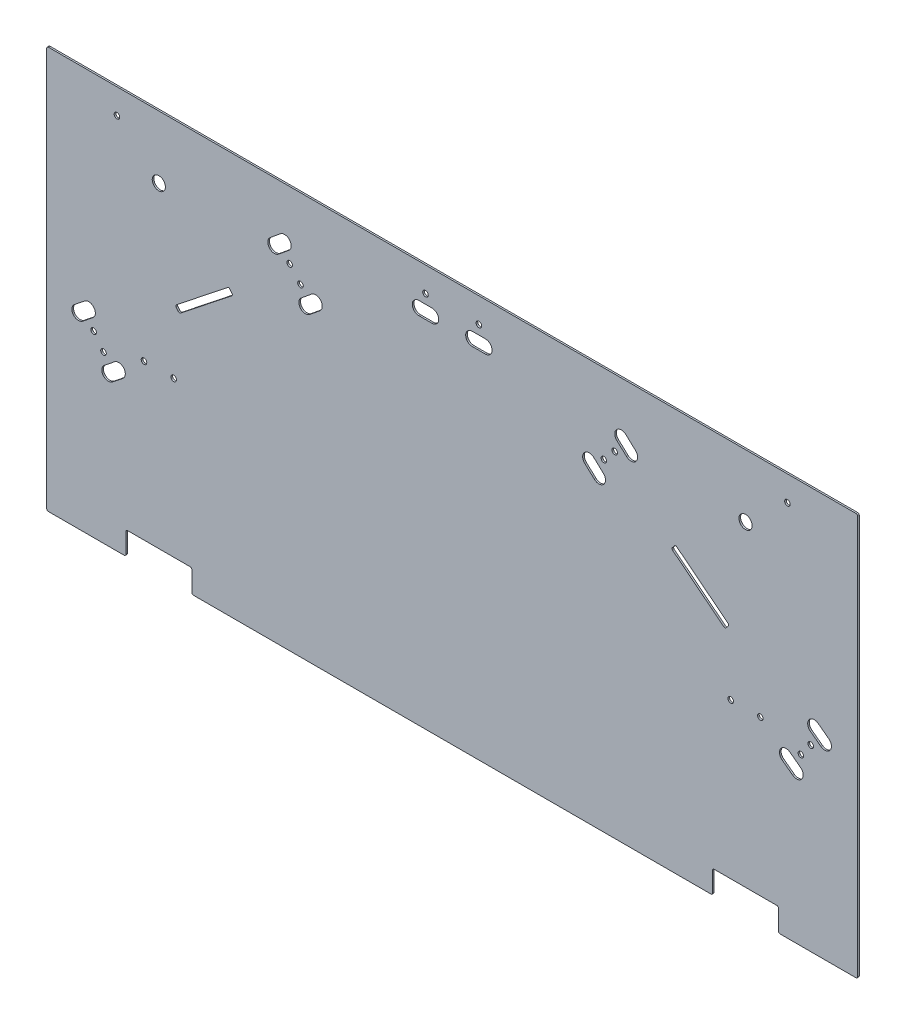
SolidWorks part; units mm, degrees
material "PE High Density"
ref_plane "Front Plane" through (0, 0, 0) normal (0, 0, 1) x (1, 0, 0)
ref_plane "Top Plane" through (0, 0, 0) normal (0, 1, 0) x (1, 0, 0)
ref_plane "Right Plane" through (0, 0, 0) normal (1, 0, 0) x (0, 0, -1)
sketch "Sketch1" plane through (0, 0, 0) normal (0, 0, 1) x (1, 0, 0)
  line L1 (-781.05, 387.35) -> (781.05, 387.35)
  line L2 (-781.05, 387.35) -> (-781.05, -387.35)
  line L3 (-781.05, -387.35) -> (781.05, -387.35)
  line L4 (781.05, 387.35) -> (781.05, -387.35)
  line L5 (-781.05, 387.35) -> (781.05, -387.35) construction
  line L6 (-781.05, -387.35) -> (781.05, 387.35) construction
  line L7 (-533.6334, 78.9622) -> (-525.7417, 69.0118)
  line L8 (-542.925, 342.9) -> (-542.925, -501.65) construction
  line L9 (542.925, 342.9) -> (542.925, -501.65) construction
  line L11 (587.375, 342.9) -> (587.375, -501.65) construction
  line L12 (-587.375, 342.9) -> (-587.375, -501.65) construction
  line L21 (-628.65, -387.35) -> (-501.65, -387.35)
  line L22 (-628.65, -387.35) -> (-628.65, -342.9)
  line L23 (-628.65, -342.9) -> (-501.65, -342.9)
  line L24 (-501.65, -387.35) -> (-501.65, -342.9)
  line L25 (628.65, -387.35) -> (501.65, -387.35)
  line L26 (628.65, -387.35) -> (628.65, -342.9)
  line L27 (628.65, -342.9) -> (501.65, -342.9)
  line L28 (501.65, -387.35) -> (501.65, -342.9)
  line L32 (-525.7417, 69.0118) -> (-422.2573, 151.0856)
  line L33 (-422.2573, 151.0856) -> (-430.149, 161.036)
  line L34 (-430.149, 161.036) -> (-533.6334, 78.9622)
  line L36 (525.8301, 69.1038) -> (422.2669, 151.078)
  line L37 (422.2669, 151.078) -> (430.149, 161.036)
  line L38 (430.149, 161.036) -> (533.7123, 79.0618)
  line L39 (533.7123, 79.0618) -> (525.8301, 69.1038)
  circle A0 centre (-51.435, 339.4592) radius 5.3578
  circle A1 centre (51.435, 339.3385) radius 5.3578
  circle A6 centre (-645.795, 339.09) radius 5.3578
  circle A7 centre (645.795, 339.09) radius 5.3578
  circle A11 centre (536.575, -44.45) radius 5.3578
  circle A12 centre (593.725, -44.45) radius 5.3578
  circle A13 centre (-593.725, -44.45) radius 5.3578
  circle A14 centre (-536.575, -44.45) radius 5.3578
  point P0 (0, 0)
  dimension "D3" = 10.7156
  dimension "D4" = 10.7156
  dimension "D7" = 729.615
  dimension "D8" = 729.615
  dimension "D19" = 135.255
  dimension "D20" = 48.26
  dimension "D21" = 10.7156
  dimension "D22" = 135.255
  dimension "D23" = 48.26
  dimension "D38" = 342.9
  dimension "D39" = 342.9
  dimension "D40" = 6.35
  dimension "D9" = 47.8908
  dimension "D14" = 350.901
  dimension "D24" = 10.7156
  dimension "D31" = 10.7156
  dimension "D32" = 10.7156
  dimension "D33" = 10.7156
  dimension "D34" = 10.7156
  dimension "D1" = 774.7
  dimension "D2" = 1562.1
  dimension "D10" = 48.0115
  dimension "D11" = 226.314
  dimension "D12" = 350.901
  dimension "D13" = 226.314
  dimension "D35" = 6.35
  dimension "D36" = 6.35
  dimension "D37" = 342.9
  dimension "D41" = 342.9
  dimension "D42" = 6.35
  dimension "D52" = 152.4
  dimension "D53" = 127
  dimension "D54" = 44.45
  dimension "D55" = 152.4
  dimension "D56" = 127
  dimension "D57" = 44.45
  dimension "D63" = 132.08
  dimension "D64" = 12.7
  dimension "D65" = 132.08
  dimension "D66" = 12.7
extrude "Boss-Extrude1" add sketch "Sketch1" along normal blind 3.175
sketch "Sketch2" plane through (0, 0, 3.175) normal (0, 0, 1) x (1, 0, 0)
  line L2 (781.05, 387.35) -> (781.05, -387.35) construction
  line L3 (628.65, -387.35) -> (781.05, -387.35) construction
  line L4 (-781.05, 387.35) -> (781.05, 387.35) construction
  line L5 (-781.05, 387.35) -> (-781.05, -387.35) construction
  line L7 (-781.05, -387.35) -> (-628.65, -387.35) construction
  circle A0 centre (-313.055, 258.318) radius 5.3578
  circle A1 centre (-292.227, 234.3543) radius 5.3578
  circle A2 centre (-690.753, -42.672) radius 5.3578
  circle A3 centre (-671.703, -68.072) radius 5.3578
  circle A4 centre (292.227, 234.3543) radius 5.3578
  circle A5 centre (313.055, 258.318) radius 5.3578
  circle A6 centre (690.753, -42.672) radius 5.3578
  circle A7 centre (671.703, -68.072) radius 5.3578
  dimension "D1" = 10.7156
  dimension "D3" = 31.75
  dimension "D8" = 129.032
  dimension "D2" = 90.297
  dimension "D4" = 344.678
  dimension "D5" = 109.347
  dimension "D6" = 31.75
  dimension "D7" = 467.995
  dimension "D9" = 488.823
  dimension "D10" = 467.995
  dimension "D11" = 488.823
  dimension "D12" = 129.032
  dimension "D13" = 31.75
  dimension "D14" = 90.297
  dimension "D15" = 109.347
  dimension "D16" = 344.678
  dimension "D17" = 31.75
extrude "Cut-Extrude1" cut sketch "Sketch2" against normal through all
sketch "Sketch3" plane through (0, 0, 3.175) normal (0, 0, 1) x (1, 0, 0)
  line L0 (-64.135, 308.9792) -> (-38.735, 308.9792) construction
  line L1 (-64.135, 321.6792) -> (-38.735, 321.6792)
  line L2 (-64.135, 296.2792) -> (-38.735, 296.2792)
  line L3 (38.735, 308.9792) -> (64.135, 308.9792) construction
  line L4 (38.735, 321.6792) -> (64.135, 321.6792)
  line L5 (38.735, 296.2792) -> (64.135, 296.2792)
  line L6 (-342.4859, 273.572) -> (-322.8733, 289.7122) construction
  line L7 (-350.556, 283.3784) -> (-330.9434, 299.5185)
  line L8 (-334.4159, 263.7657) -> (-314.8032, 279.9059)
  line L9 (-282.6651, 202.7491) -> (-263.0525, 218.8893) construction
  line L10 (-290.7352, 212.5554) -> (-271.1226, 228.6956)
  line L11 (-274.595, 192.9428) -> (-254.9824, 209.083)
  line L12 (-719.9479, -26.9932) -> (-700.1126, -11.1275) construction
  line L13 (-727.8807, -17.0755) -> (-708.0454, -1.2098)
  line L14 (-712.015, -36.9108) -> (-692.1797, -21.0451)
  line L15 (-662.2696, -99.5575) -> (-642.4343, -83.6918) construction
  line L16 (-670.2025, -89.6398) -> (-650.3672, -73.7742)
  line L17 (-654.3368, -109.4752) -> (-634.5015, -93.6095)
  line L18 (325.9271, 287.9302) -> (344.5749, 270.6843) construction
  line L19 (334.55, 297.2541) -> (353.1978, 280.0082)
  line L20 (317.3041, 278.6063) -> (335.952, 261.3604)
  line L21 (264.0577, 218.8893) -> (282.7056, 201.6434) construction
  line L22 (272.6807, 228.2132) -> (291.3285, 210.9673)
  line L23 (255.4348, 209.5654) -> (274.0826, 192.3195)
  line L24 (643.2495, -84.8267) -> (663.5646, -100.0734) construction
  line L25 (650.8729, -74.6692) -> (671.1879, -89.9158)
  line L26 (635.6262, -94.9843) -> (655.9413, -110.2309)
  line L27 (697.5841, -9.6895) -> (717.8992, -24.9361) construction
  line L28 (705.2074, 0.468) -> (725.5225, -14.7786)
  line L29 (689.9608, -19.847) -> (710.2758, -35.0936)
  line L30 (-781.05, 387.35) -> (781.05, 387.35) construction
  arc A0 (-64.135, 321.6792) -> (-64.135, 296.2792) centre (-64.135, 308.9792) ccw
  arc A1 (-38.735, 296.2792) -> (-38.735, 321.6792) centre (-38.735, 308.9792) ccw
  arc A2 (38.735, 321.6792) -> (38.735, 296.2792) centre (38.735, 308.9792) ccw
  arc A3 (64.135, 296.2792) -> (64.135, 321.6792) centre (64.135, 308.9792) ccw
  arc A4 (-350.556, 283.3784) -> (-334.4159, 263.7657) centre (-342.4859, 273.572) ccw
  arc A5 (-314.8032, 279.9059) -> (-330.9434, 299.5185) centre (-322.8733, 289.7122) ccw
  arc A6 (-290.7352, 212.5554) -> (-274.595, 192.9428) centre (-282.6651, 202.7491) ccw
  arc A7 (-254.9824, 209.083) -> (-271.1226, 228.6956) centre (-263.0525, 218.8893) ccw
  arc A8 (-727.8807, -17.0755) -> (-712.015, -36.9108) centre (-719.9479, -26.9932) ccw
  arc A9 (-692.1797, -21.0451) -> (-708.0454, -1.2098) centre (-700.1126, -11.1275) ccw
  arc A10 (-670.2025, -89.6398) -> (-654.3368, -109.4752) centre (-662.2696, -99.5575) ccw
  arc A11 (-634.5015, -93.6095) -> (-650.3672, -73.7742) centre (-642.4343, -83.6918) ccw
  arc A12 (334.55, 297.2541) -> (317.3041, 278.6063) centre (325.9271, 287.9302) ccw
  arc A13 (335.952, 261.3604) -> (353.1978, 280.0082) centre (344.5749, 270.6843) ccw
  arc A14 (272.6807, 228.2132) -> (255.4348, 209.5654) centre (264.0577, 218.8893) ccw
  arc A15 (274.0826, 192.3195) -> (291.3285, 210.9673) centre (282.7056, 201.6434) ccw
  arc A16 (650.8729, -74.6692) -> (635.6262, -94.9843) centre (643.2495, -84.8267) ccw
  arc A17 (655.9413, -110.2309) -> (671.1879, -89.9158) centre (663.5646, -100.0734) ccw
  arc A18 (705.2074, 0.468) -> (689.9608, -19.847) centre (697.5841, -9.6895) ccw
  arc A19 (710.2758, -35.0936) -> (725.5225, -14.7786) centre (717.8992, -24.9361) ccw
  circle A20 centre (-51.435, 339.4592) radius 5.3578 construction
  circle A21 centre (-313.055, 258.318) radius 5.3578 construction
  circle A22 centre (-292.227, 234.3543) radius 5.3578 construction
  circle A23 centre (-690.753, -42.672) radius 5.3578 construction
  circle A24 centre (-671.703, -68.072) radius 5.3578 construction
  circle A25 centre (292.227, 234.3543) radius 5.3578 construction
  circle A26 centre (313.055, 258.318) radius 5.3578 construction
  circle A27 centre (671.703, -68.072) radius 5.3578 construction
  circle A28 centre (690.753, -42.672) radius 5.3578 construction
  point P2 (-51.435, 308.9792)
  point P7 (51.435, 308.9792)
  point P14 (-332.6796, 281.6421)
  point P21 (-272.8588, 210.8192)
  point P28 (-710.0302, -19.0603)
  point P35 (-652.352, -91.6247)
  point P42 (335.251, 279.3073)
  point P49 (273.3817, 210.2664)
  point P56 (653.4071, -92.45)
  point P63 (707.7416, -17.3128)
  dimension "D3" = 17.78
  dimension "D5" = 17.78
  dimension "D1" = 25.4
  dimension "D2" = 25.4
  dimension "D4" = 17.78
  dimension "D6" = 17.78
  dimension "D7" = 17.78
  dimension "D8" = 17.78
  dimension "D9" = 17.78
  dimension "D10" = 17.78
  dimension "D11" = 17.78
extrude "Cut-Extrude2" cut sketch "Sketch3" against normal through all
fillet "Fillet1" radius 3.175 20 edges at (-525.7417, 69.0118, 1.5875) (-533.6334, 78.9622, 1.5875) (-430.149, 161.036, 1.5875) (-422.2573, 151.0856, 1.5875) (-628.65, -342.9, 1.5875) (-501.65, -342.9, 1.5875) (628.65, -342.9, 1.5875) (501.65, -342.9, 1.5875) (525.8301, 69.1038, 1.5875) (533.7123, 79.0618, 1.5875) (430.149, 161.036, 1.5875) (422.2669, 151.078, 1.5875) (-781.05, 387.35, 1.5875) (-781.05, -387.35, 1.5875) (-628.65, -387.35, 1.5875) (-501.65, -387.35, 1.5875) (501.65, -387.35, 1.5875) (628.65, -387.35, 1.5875) (781.05, -387.35, 1.5875) (781.05, 387.35, 1.5875)
sketch "Sketch4" plane through (0, 0, 3.175) normal (0, 0, 1) x (1, 0, 0)
  line L0 (-777.875, 387.35) -> (777.875, 387.35) construction
  point P0 (-565.15, 266.7)
  point P1 (565.15, 266.7)
  point P4 (0, 0)
  dimension "D1" = 1130.3
  dimension "D2" = 565.15
  dimension "D3" = 120.65
hole_wizard "1 (1) Diameter Hole1" positions "Sketch5" profile "Sketch6" hole size "1" standard "ANSI Inch" end condition up to next
sketch "Sketch5" plane through (0, 0, 3.175) normal (0, 0, 1) x (1, 0, 0)
  point P0 (-565.15, 266.7)
  point P3 (565.15, 266.7)
sketch "Sketch6" plane through (-565.15, 266.7, 3.175) normal (1, 0, 0) x (0, -1, 0)
  line L0 (0, 0) -> (0, 3.175)
  line L1 (0, 3.175) -> (12.7, 3.175)
  line L2 (12.7, 3.175) -> (12.7, 0)
  line L5 (12.7, 0) -> (0, 0)
  line L11 (0, -6.35) -> (0, 107.95) construction
  dimension "Thru Hole Dia." = 25.4
  dimension "Thru Hole Depth" = 3.175
equation "\"D2@Sketch4\"=\"D1@Sketch4\"/2"
